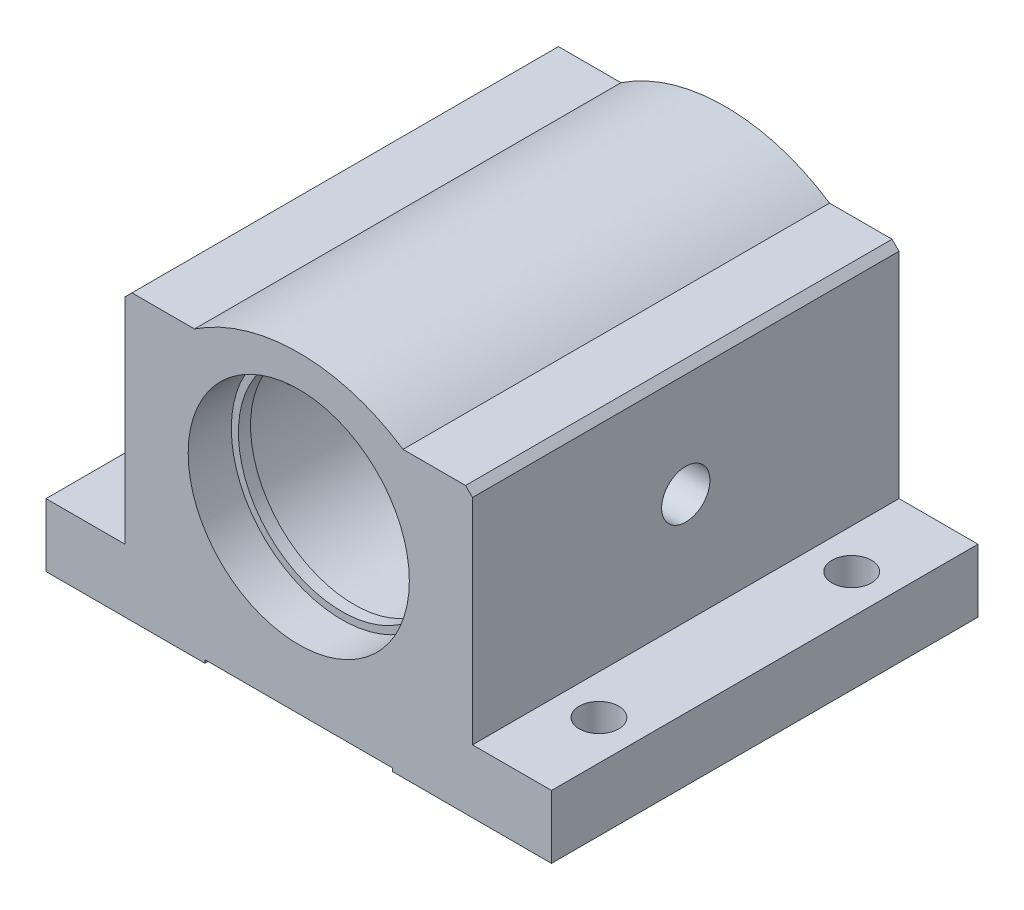
SolidWorks part; units mm, degrees
ref_plane "Front Plane" through (0, 0, 0) normal (0, 0, 1) x (1, 0, 0)
ref_plane "Top Plane" through (0, 0, 0) normal (0, 1, 0) x (1, 0, 0)
ref_plane "Right Plane" through (0, 0, 0) normal (1, 0, 0) x (0, 0, -1)
sketch "Sketch1" plane through (0, 0, 0) normal (0, 0, 1) x (1, 0, 0)
  line L0 (-25.4, -9.525) -> (-17.4625, -9.525)
  line L1 (-25.4, 15.875) -> (25.4, 15.875)
  line L2 (-25.4, 15.875) -> (-25.4, -15.875)
  line L3 (-25.4, -15.875) -> (25.4, -15.875)
  line L4 (25.4, 15.875) -> (25.4, -15.875)
  line L5 (-17.4625, -9.525) -> (-17.4625, 12.7)
  line L6 (-17.4625, 12.7) -> (17.4625, 12.7)
  line L7 (17.4625, 12.7) -> (17.4625, -9.525)
  line L8 (17.4625, -9.525) -> (25.4, -9.525)
  line L9 (0, 1.5748) -> (0, -15.875) construction
  circle A0 centre (0, 1.5748) radius 11.1125
  point P4 (25.4, 0)
  point P5 (0, 15.875)
  dimension "ID | For Bearing OD" = 22.225
  dimension "Overall Height" = 31.75
  dimension "Overall Width" = 50.8
  dimension "Base Thickness" = 6.35
  dimension "K" = 28.575
  dimension "G" = 34.925
  dimension "Center Height" = 17.4498
sketch "Sketch2" plane through (0, 0, 0) normal (1, 0, 0) x (0, 0, -1)
  line L0 (-21.4312, 0) -> (21.4312, 0) construction
  line L2 (0, 15.875) -> (0, -15.875) construction
  line L3 (0, 15.875) -> (0, -15.875) construction
  circle A0 centre (0, 1.5748) radius 2.4257
  point P2 (0, 0)
  point P11 (-15.875, 0)
  dimension "Grease Hole Diameter" = 4.8514
  dimension "Overall Length" = 42.8625
  dimension "For Maximum Bearing Length" = 31.75
sketch "Sketch3" plane through (0, 0, 0) normal (0, 1, 0) x (1, 0, 0)
  line L1 (-25.4, 21.4312) -> (25.4, 21.4313)
  line L2 (-25.4, 21.4312) -> (-25.4, -21.4313)
  line L3 (-25.4, -21.4313) -> (25.4, -21.4313)
  line L4 (25.4, 21.4313) -> (25.4, -21.4313)
  line L5 (-21.4376, 12.7) -> (21.4376, 12.7) construction
  line L6 (-21.4376, 12.7) -> (-21.4376, -12.7) construction
  line L7 (-21.4376, -12.7) -> (21.4376, -12.7) construction
  line L8 (21.4376, 12.7) -> (21.4376, -12.7) construction
  circle A0 centre (-21.4376, 12.7) radius 1.9844
  point P4 (0, 21.4312)
  point P5 (25.4, 0)
  point P12 (0, 12.7)
  point P13 (21.4376, 0)
  dimension "Mounting Hole Diameter" = 3.9688
  dimension "Mounting Hole Center to Center, Length" = 25.4
  dimension "Mounting Hole Center to Center, Width" = 42.8752
sketch "Sketch4" plane through (0, 0, 0) normal (0, 0, 1) x (1, 0, 0)
  line L0 (-25.4, -9.525) -> (-17.4625, -9.525) construction
  line L1 (-25.4, -9.525) -> (-17.4625, -9.525)
  line L2 (-25.4, -15.875) -> (25.4, -15.875) construction
  line L3 (17.4625, -9.525) -> (25.4, -9.525) construction
  line L4 (17.4625, 12.7) -> (17.4625, -9.525) construction
  line L5 (-17.4625, 12.7) -> (17.4625, 12.7) construction
  line L6 (-17.4625, -9.525) -> (-17.4625, 12.7) construction
  line L7 (-25.4, -15.875) -> (-9.4298, -15.875)
  line L8 (17.4625, -9.525) -> (25.4, -9.525)
  line L9 (17.4625, 12.7) -> (17.4625, -9.525)
  line L10 (-17.4625, 12.7) -> (-10.4775, 12.7)
  line L11 (-17.4625, -9.525) -> (-17.4625, 12.7)
  line L12 (-25.4, -9.525) -> (-25.4, -15.875)
  line L13 (25.4, -9.525) -> (25.4, -15.875)
  line L14 (10.4775, 12.7) -> (17.4625, 12.7)
  line L15 (-25.4, 15.875) -> (25.4, 15.875) construction
  line L16 (-9.4298, -15.875) -> (-9.4297, -15.5575)
  line L17 (-9.4297, -15.5575) -> (9.4297, -15.5575)
  line L18 (9.4297, -15.5575) -> (9.4298, -15.875)
  line L19 (0, 1.5748) -> (0, -15.875) construction
  line L22 (9.4298, -15.875) -> (25.4, -15.875)
  circle A0 centre (0, 1.5748) radius 11.1125 construction
  circle A1 centre (0, 1.5748) radius 11.1125
  arc A2 (-10.4775, 12.7) -> (10.4775, 12.7) centre (0, -3.0004) cw
  point P14 (0, 15.875)
  point P17 (0, 15.875)
  point P20 (0, -15.5575)
  dimension "D1" = 20.955
  dimension "D2" = 18.8595
  dimension "D3" = 0.3175
extrude "Boss-Extrude1" add sketch "Sketch4" along normal up to vertex (21.4312 mm away) from vertex up to point (0, 0, 21.4312) starting at point (0, 0, -21.4312)
sketch "Sketch5" plane through (0, -9.525, 0) normal (0, 1, 0) x (1, 0, 0)
  circle A0 centre (-21.4376, 12.7) radius 1.9844 construction
  circle A1 centre (-21.4376, 12.7) radius 1.9844
  circle A2 centre (21.4376, 12.7) radius 1.9844
  circle A3 centre (21.4376, -12.7) radius 1.9844
  circle A4 centre (-21.4376, -12.7) radius 1.9844
extrude "Cut-Extrude1" cut sketch "Sketch5" against normal through all
chamfer "Chamfer1" distance 0.6985 angle 45 2 edges at (-17.4625, 12.7, 0) (17.4625, 12.7, 0)
ref_plane "Plane1" through (0, 0, 15.875) normal (0, 0, 1) x (1, 0, 0)
sketch "Sketch6" plane through (0, 0, 15.875) normal (0, 0, 1) x (1, 0, 0)
  circle A0 centre (0, 1.5748) radius 11.8237
  dimension "Retaining Ring Slot OD" = 23.6474
extrude "Cut-Extrude2" cut sketch "Sketch6" along normal blind 1.2192
mirror "Mirror1" about plane through (0, 0, 0) normal (0, 0, 1) of "Cut-Extrude2"
sketch "Sketch7" plane through (17.4625, 0, 0) normal (1, 0, 0) x (0, 0, -1)
  circle A0 centre (0, 1.5748) radius 2.4257 construction
  circle A1 centre (0, 1.5748) radius 2.4257
extrude "Cut-Extrude3" cut sketch "Sketch7" against normal up to next
sketch "Sketch8" plane through (0, 0, 15.875) normal (0, 0, 1) x (1, 0, 0)
  line L0 (0, 1.5748) -> (-6.8519, 8.4267) construction
  line L1 (6.8519, 8.4267) -> (8.3606, 9.9354) construction
  line L2 (0, 1.5748) -> (0, 15.875) construction
  line L3 (0, -10.2489) -> (0, -9.5377) construction
  line L4 (0, -9.5377) -> (0, -8.8265) construction
  line L5 (-4.3582, 9.9492) -> (-5.1789, 12.204)
  line L6 (-6.8748, 8.9506) -> (-6.3788, 8.5343)
  line L7 (-5.558, 9.5125) -> (-4.8256, 8.4665) construction
  line L8 (0, -8.8265) -> (0, -8.1153) construction
  line L9 (-4.8256, 8.4665) -> (0, 1.5748) construction
  line L10 (-7.3548, 8.9296) -> (-8.3606, 9.9354) construction
  line L11 (-7.3548, 8.9296) -> (-7.1034, 8.6782) construction
  line L12 (-7.1034, 8.6782) -> (-6.8519, 8.4267) construction
  line L13 (6.8748, 8.9506) -> (6.3788, 8.5343)
  line L14 (4.3582, 9.9492) -> (5.1789, 12.204)
  circle A0 centre (0, 1.5748) radius 11.8237 construction
  arc A1 (-8.3606, 9.9354) -> (8.3606, 9.9354) centre (0, 1.5748) ccw
  arc A2 (-7.3548, 8.9296) -> (7.3548, 8.9296) centre (0, 1.5748) ccw
  circle A3 centre (0, 1.5748) radius 11.1125 construction
  arc A4 (10.4775, 12.7) -> (-10.4775, 12.7) centre (0, -3.0004) ccw construction
  arc A6 (-7.3548, 8.9296) -> (-6.8748, 8.9506) centre (-7.1034, 8.6782) cw
  arc A9 (-8.3606, 9.9354) -> (-5.1789, 12.204) centre (0, 1.5748) cw
  arc A10 (-6.3788, 8.5343) -> (-4.3582, 9.9492) centre (-5.558, 9.5125) ccw
  circle A11 centre (0, 1.5748) radius 9.6901 construction
  circle A12 centre (-5.558, 9.5125) radius 0.6384
  arc A13 (7.3548, 8.9296) -> (6.8748, 8.9506) centre (7.1034, 8.6782) ccw
  circle A14 centre (5.558, 9.5125) radius 0.6384
  arc A15 (6.3788, 8.5343) -> (4.3582, 9.9492) centre (5.558, 9.5125) cw
  arc A16 (8.3606, 9.9354) -> (5.1789, 12.204) centre (0, 1.5748) ccw
  point P20 (-5.1918, 8.9895)
  dimension "D3" = 30
  dimension "D4" = 10
  dimension "D1" = 45
extrude "Boss-Extrude2" add sketch "Sketch8" along normal blind 1.2192 separate body
mirror "Mirror2" about plane through (0, 0, 0) normal (0, 0, 1) of bodies 109
equation "\"D1@Sketch4\"=0.6*\"G@Sketch1\""
equation "\"D2@Sketch4\"=\"D1@Sketch4\"*.9"
equation "\"D1@Chamfer1\"=.02*\"G@Sketch1\""
equation "\"D3@Sketch4\"=.05*\"Base Thickness@Sketch1\""
equation "\"D1@Boss-Extrude2\"=\"Retaining Ring Slot Thickness@Cut-Extrude2\""
